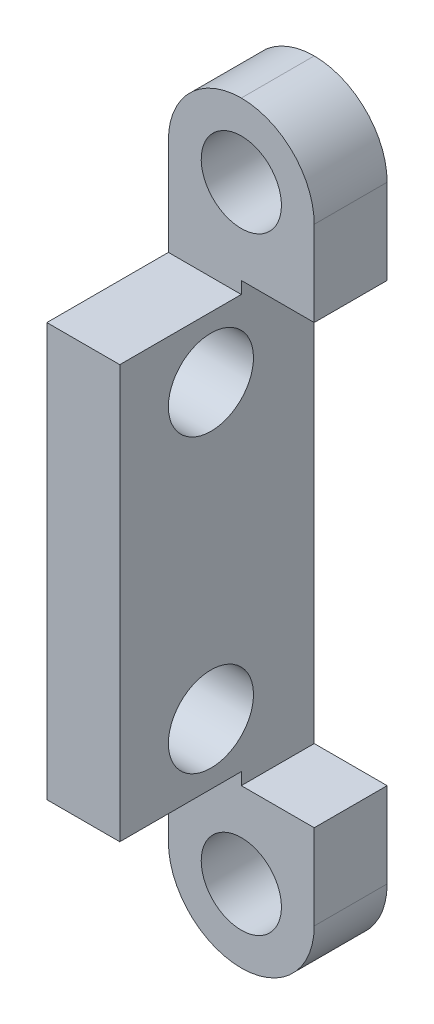
SolidWorks part; units mm, degrees
ref_plane "Face" through (0, 0, 0) normal (0, 0, 1) x (1, 0, 0)
ref_plane "Dessus" through (0, 0, 0) normal (0, 1, 0) x (1, 0, 0)
ref_plane "Droite" through (0, 0, 0) normal (1, 0, 0) x (0, 0, -1)
sketch "Esquisse1" plane through (0, 0, 0) normal (0, 0, 1) x (1, 0, 0)
  line L0 (3, 0) -> (3, 31) construction
  line L1 (0, 0) -> (6, 0)
  line L2 (0, 0) -> (0, 31)
  line L3 (0, 31) -> (6, 31)
  line L4 (6, 0) -> (6, 6.5)
  line L5 (0, 15.5) -> (14.1239, 15.5) construction
  line L6 (6, 24.5) -> (3, 24.5)
  line L7 (3, 24.5) -> (3, 6.5)
  line L8 (3, 6.5) -> (6, 6.5)
  line L9 (6, 24.5) -> (6, 31)
  circle A0 centre (3, 28) radius 1.65
  circle A1 centre (3, 3) radius 1.65
  point P18 (4.5, 6.5)
  dimension "D3" = 25
  dimension "D4" = 3.3
  dimension "D1" = 31
  dimension "D2" = 6
  dimension "D5" = 3
  dimension "D6" = 3.5
  dimension "D7" = 3.5
  dimension "D8" = 3
extrude "Boss.-Extru.1" add sketch "Esquisse1" along normal blind 8
sketch "Esquisse2" plane through (0, 0, 0) normal (-1, 0, 0) x (0, 0, 1)
  line L0 (4.25, 32) -> (4.25, 0) construction
  line L3 (8, 15.5) -> (0, 15.5) construction
  line L4 (8, 31) -> (8, 0) construction
  line L5 (0, 31) -> (0, 0) construction
  circle A0 centre (4.25, 21.5) radius 1.75
  circle A1 centre (4.25, 9.5) radius 1.75
  point P2 (0, 0)
  point P3 (0, 0)
  point P16 (0, 0)
  point P17 (0, 0)
  dimension "D1" = 3.5
  dimension "D2" = 12
  dimension "D3" = 6
  dimension "D4" = 3.75
extrude "Enlèv. mat.-Extru.1" cut sketch "Esquisse2" against normal through all
fillet "Congé1" radius 3 4 edges at (6, 0, 4) (0, 0, 4) (0, 31, 4) (6, 31, 4)
sketch "Esquisse3" plane through (0, 0, 0) normal (-1, 0, 0) x (0, 0, 1)
  line L0 (0, 28) -> (0, 3) construction
  line L1 (8, 31) -> (3, 31)
  line L2 (8, 31) -> (8, 24)
  line L3 (8, 24) -> (3, 24)
  line L4 (3, 31) -> (3, 24)
  line L5 (8, 31) -> (3, 24) construction
  line L6 (8, 24) -> (3, 31) construction
  line L7 (8, 0) -> (3, 0)
  line L8 (8, 0) -> (8, 7)
  line L9 (8, 7) -> (3, 7)
  line L10 (3, 0) -> (3, 7)
  line L11 (8, 0) -> (3, 7) construction
  line L12 (8, 7) -> (3, 0) construction
  line L13 (0, 31) -> (8, 31) construction
  line L14 (8, 0) -> (0, 0) construction
  point P4 (5.5, 27.5)
  point P10 (5.5, 3.5)
  point P14 (0, 0)
  point P15 (0, 0)
  point P16 (0, 0)
  point P18 (0, 0)
  point P19 (0, 0)
  point P20 (0, 0)
  point P21 (0, 0)
  point P22 (0, 0)
  point P23 (0, 0)
  dimension "D1" = 3
  dimension "D2" = 7
extrude "Enlèv. mat.-Extru.2" cut sketch "Esquisse3" against normal through all
